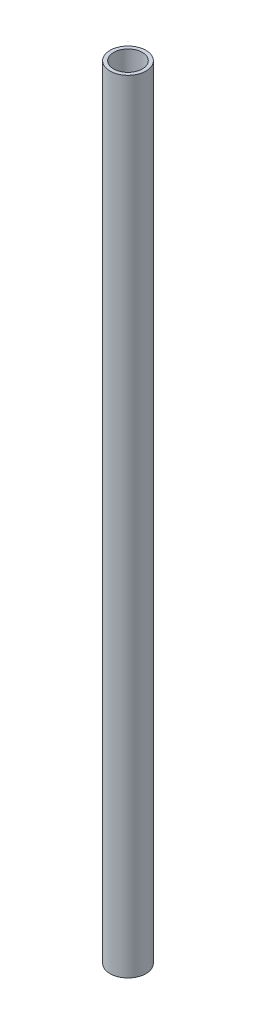
SolidWorks part; units mm, degrees
ref_plane "Front Plane" through (0, 0, 0) normal (0, 0, 1) x (1, 0, 0)
ref_plane "Top Plane" through (0, 0, 0) normal (0, 1, 0) x (1, 0, 0)
ref_plane "Right Plane" through (0, 0, 0) normal (1, 0, 0) x (0, 0, -1)
sketch "Sketch1" plane through (0, 0, 0) normal (0, 1, 0) x (1, 0, 0)
  circle A0 centre (0, 0) radius 17.5
  circle A1 centre (0, 0) radius 14
  dimension "D1" = 35
  dimension "D2" = 28
extrude "Boss-Extrude1" add sketch "Sketch1" against normal mid plane 762
sketch "Sketch2" plane through (0, 0, 0) normal (0, 0, 1) x (1, 0, 0)
  line L2 (-3.5, 331) -> (-3.5, 306)
  line L4 (8.5, 331) -> (8.5, 306)
  line L7 (17.5, -381) -> (17.5, 381) construction
  line L8 (17.5, 381) -> (-17.5, 381) construction
  arc A0 (-3.5, 306) -> (8.5, 306) centre (2.5, 306) ccw
  arc A1 (-3.5, 331) -> (8.5, 331) centre (2.5, 331) cw
  dimension "D4" = 15
  dimension "D1" = 6
  dimension "D3" = 6
  dimension "D5" = 25
  dimension "D2" = 50
extrude "Cut-Extrude1" cut sketch "Sketch2" against normal blind 12
